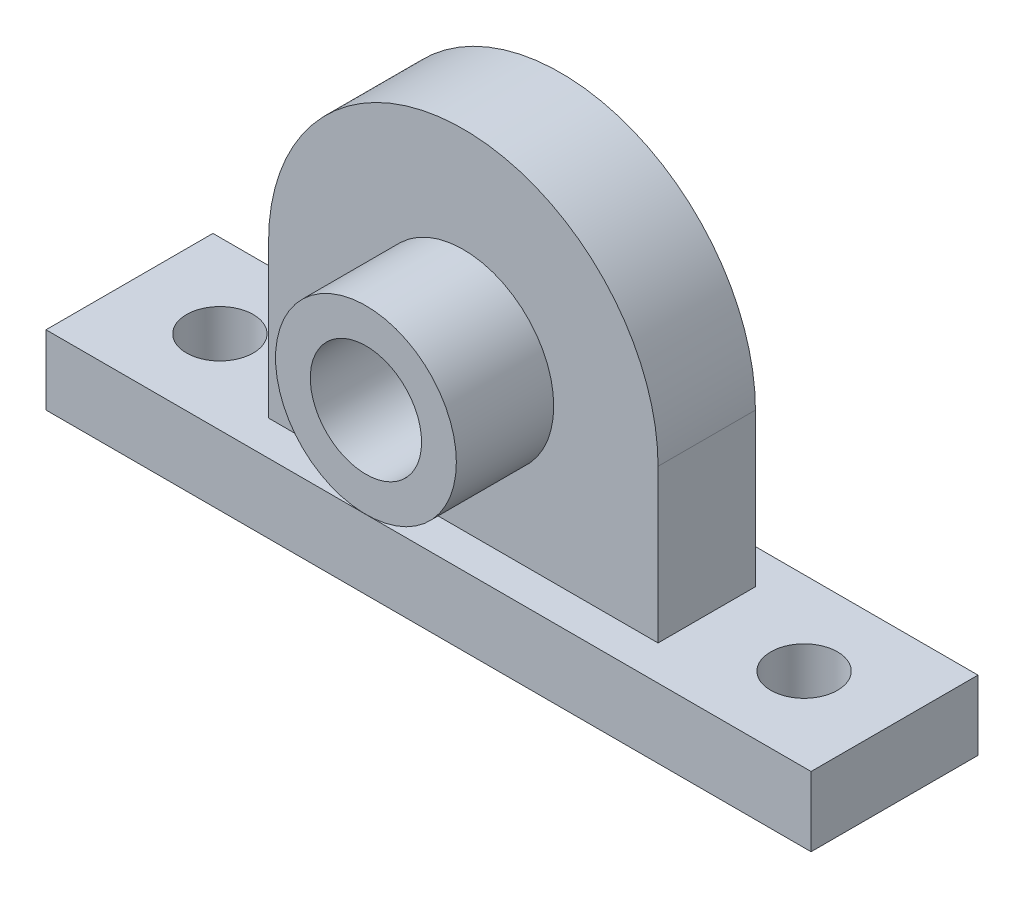
SolidWorks part; units mm, degrees
material "AISI 304"
ref_plane "前视基准面" through (0, 0, 0) normal (0, 0, 1) x (1, 0, 0)
ref_plane "上视基准面" through (0, 0, 0) normal (0, 1, 0) x (1, 0, 0)
ref_plane "右视基准面" through (0, 0, 0) normal (1, 0, 0) x (0, 0, -1)
sketch "Sketch1" plane through (0, 0, 0) normal (0, 0, 1) x (1, 0, 0)
  line L0 (0, 27.5) -> (16.1857, 27.5) construction
  line L1 (-27.5, 2.5) -> (27.5, 2.5)
  line L2 (-27.5, 2.5) -> (-27.5, -2.5)
  line L3 (-27.5, -2.5) -> (27.5, -2.5)
  line L4 (27.5, 2.5) -> (27.5, -2.5)
  line L5 (0, -2.5) -> (0, 2.5) construction
  line L6 (-27.5, 0) -> (27.5, 0) construction
  line L7 (-14, 13.5) -> (-14, 2.5)
  line L8 (14, 13.5) -> (14, 2.5)
  circle A0 centre (0, 13.5) radius 4
  arc A1 (8.6603, 2.5) -> (-8.6603, 2.5) centre (0, 13.5) ccw
  circle A2 centre (0, 13.5) radius 6.5
  point P0 (0, 0)
  dimension "D3" = 8
  dimension "D5" = 30
  dimension "D6" = 13
  dimension "D1" = 55
  dimension "D2" = 5
  dimension "D4" = 16
extrude "Boss-Extrude1" add sketch "Sketch1" along normal mid plane 12 contours L4 L1 L2 L3 region at (0, 0, 0)
extrude "Boss-Extrude2" add sketch "Sketch1<4>" along normal mid plane 7 contours A1 L7 L1 | A1 L1 A2 | A1 L1 L8 region at (-12.4686, 5.1341, 0) region at (-12.2568, 7.5501, 0) region at (12.4686, 5.1341, 0)
sketch "Sketch1<4>" plane through (0, 0, 0) normal (0, 0, 1) x (1, 0, 0) same geometry as "Sketch1"
extrude "Boss-Extrude3" add sketch "Sketch1<5>" along normal blind 10.5 and the other way blind 3.5 contours A2 A0 region at (-6.3162, 13.5, 0)
sketch "Sketch1<5>" plane through (0, 0, 0) normal (0, 0, 1) x (1, 0, 0) same geometry as "Sketch1"
sketch "Sketch2" plane through (0, -2.5, 0) normal (0, -1, 0) x (1, 0, 0)
  circle A0 centre (21, 0) radius 2.4
  circle A1 centre (-21, 0) radius 2.4
  dimension "D3" = 4.8
  dimension "D1" = 21
  dimension "D2" = 21
extrude "Cut-Extrude1" cut sketch "Sketch2" against normal up to next
